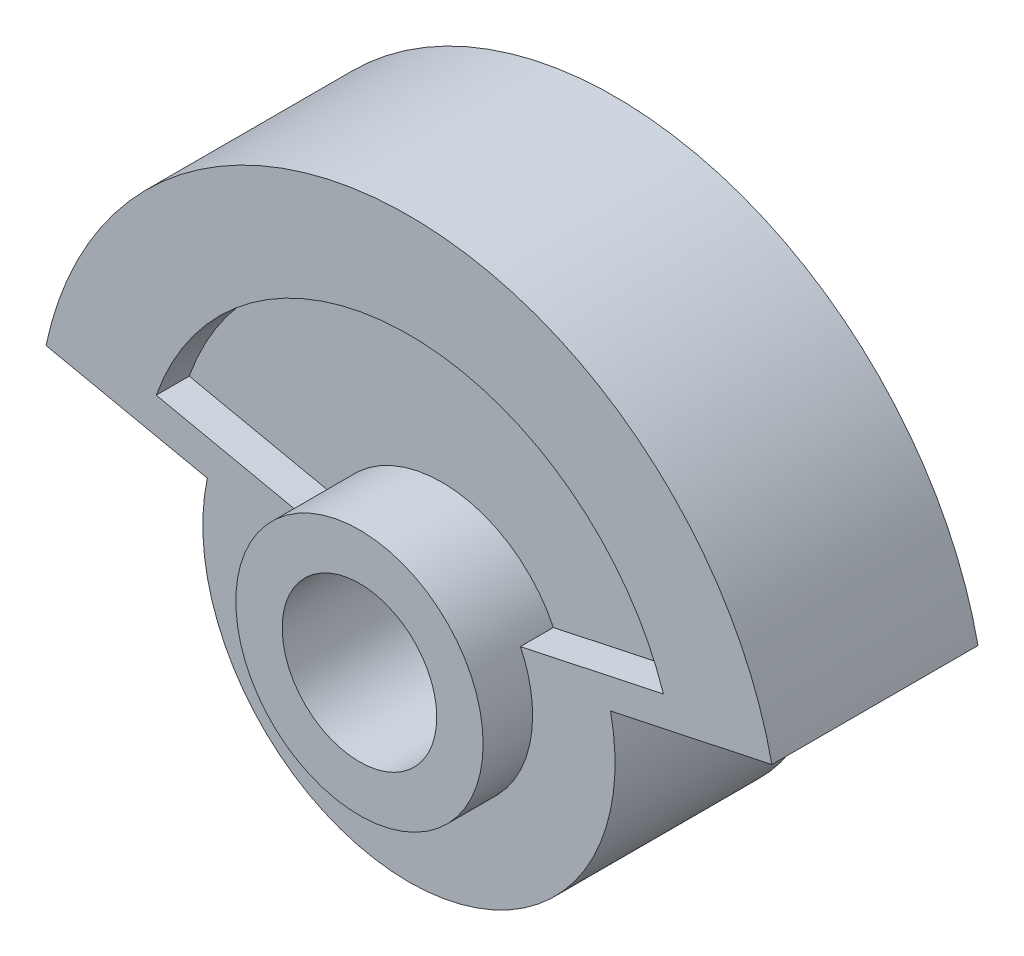
SolidWorks part; units mm, degrees
note: The reader was unsure of these and kept them because the rebuilt part matched: shared geometry of "Sketch3<2>".
ref_plane "Front Plane" through (0, 0, 0) normal (0, 0, 1) x (1, 0, 0)
ref_plane "Top Plane" through (0, 0, 0) normal (0, 1, 0) x (1, 0, 0)
ref_plane "Right Plane" through (0, 0, 0) normal (1, 0, 0) x (0, 0, -1)
sketch "Sketch1" plane through (0, 0, 0) normal (0, 0, 1) x (1, 0, 0)
  line L0 (4.8908, 1.0391) -> (8.8035, 1.8703)
  line L1 (-4.8908, 1.0391) -> (-8.8035, 1.8703)
  arc A0 (8.8035, 1.8703) -> (-8.8035, 1.8703) centre (0, 0) ccw
  circle A2 centre (0, 0) radius 5
  dimension "D1" = 4
  dimension "D2" = 9
extrude "Boss-Extrude3" add sketch "Sketch1" along normal blind 6.2 contours A2 L0 A0 L1 | A2
sketch "Sketch3" plane through (0, 0, 6.2) normal (0, 0, 1) x (1, 0, 0)
  circle A0 centre (0, 0) radius 1.875
  dimension "D1" = 3.75
extrude "Cut-Extrude2" cut sketch "Sketch3<2>" against normal blind 10
sketch "Sketch3<2>" plane through (0, 0, 6.2) normal (0, 0, 1) x (1, 0, 0) same geometry as "Sketch3"
sketch "Sketch4" plane through (0, 0, 6.2) normal (0, 0, 1) x (1, 0, 0)
  line L0 (2.7041, 1.2992) -> (6.1728, 2.0362)
  line L1 (-2.6417, 1.4217) -> (-6.1297, 2.1627)
  line L2 (4.8908, 1.0391) -> (8.8035, 1.8703) construction
  line L3 (-4.8908, 1.0391) -> (-8.8035, 1.8703) construction
  arc A0 (2.7041, 1.2992) -> (-2.6417, 1.4217) centre (0, 0) ccw
  arc A1 (6.1728, 2.0362) -> (-6.1297, 2.1627) centre (0, 0) ccw
  dimension "D1" = 3
  dimension "D2" = 6.5
extrude "Cut-Extrude3" cut sketch "Sketch4" against normal blind 2
sketch "Sketch5" plane through (0, 0, 6.2) normal (0, 0, 1) x (1, 0, 0)
  circle A0 centre (0, 0) radius 3
  circle A1 centre (0, 0) radius 10.3441
  dimension "D1" = 6
extrude "Cut-Extrude4" cut sketch "Sketch5" against normal blind 1.2
extrude "Cut-Extrude1" cut sketch "Sketch3" against normal up to surface (5 mm away)
